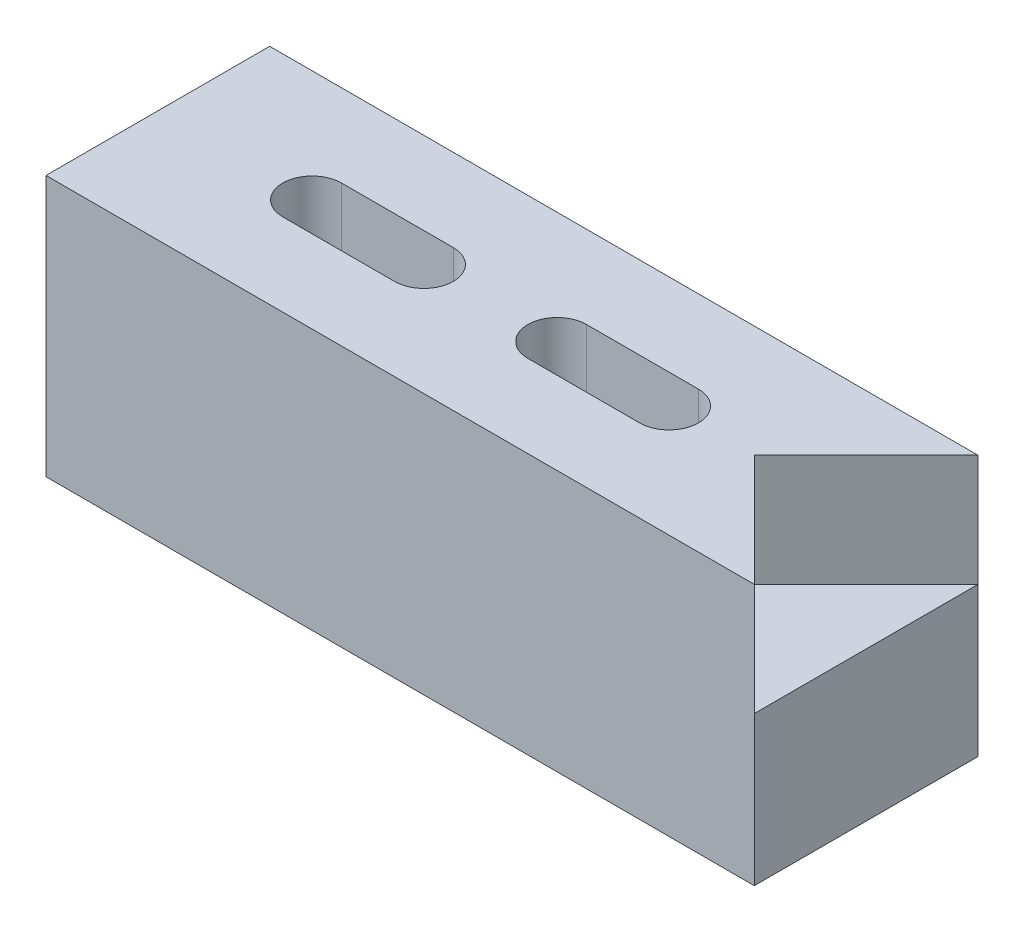
SolidWorks part; units mm, degrees
ref_plane "Front Plane" through (0, 0, 0) normal (0, 0, 1) x (1, 0, 0)
ref_plane "Top Plane" through (0, 0, 0) normal (0, 1, 0) x (1, 0, 0)
ref_plane "Right Plane" through (0, 0, 0) normal (1, 0, 0) x (0, 0, -1)
sketch "Sketch1" plane through (0, 0, 0) normal (0, 0, 1) x (1, 0, 0)
  line L0 (0, 0) -> (48.26, 0)
  line L6 (0, 0) -> (0, 17.78)
  line L10 (0, 17.78) -> (48.26, 17.78)
  line L11 (48.26, 0) -> (48.26, 17.78)
  dimension "D1" = 48.26
  dimension "D2" = 17.78
extrude "Boss-Extrude1" add sketch "Sketch1" against normal blind 15.24
sketch "Sketch3" plane through (0, 17.78, 0) normal (0, 1, 0) x (1, 0, 0)
  line L0 (48.26, 15.24) -> (40.64, 7.62)
  line L1 (40.64, 7.62) -> (48.26, 0)
  line L4 (48.26, 15.24) -> (48.26, 0)
  point P5 (36.83, 6.35)
  dimension "D2" = 90
extrude "Cut-Extrude1" cut sketch "Sketch3" against normal blind 7.62
sketch "Sketch4" plane through (0, 17.78, 0) normal (0, 1, 0) x (1, 0, 0)
  line L0 (34.83, 7.62) -> (27.21, 7.62) construction
  line L1 (34.83, 5.62) -> (27.21, 5.62)
  line L2 (34.83, 9.62) -> (27.21, 9.62)
  line L3 (18.13, 7.62) -> (10.51, 7.62) construction
  line L4 (18.13, 5.62) -> (10.51, 5.62)
  line L5 (18.13, 9.62) -> (10.51, 9.62)
  line L6 (48.26, 0) -> (0, 0) construction
  arc A0 (34.83, 5.62) -> (34.83, 9.62) centre (34.83, 7.62) ccw
  arc A1 (27.21, 9.62) -> (27.21, 5.62) centre (27.21, 7.62) ccw
  arc A2 (18.13, 5.62) -> (18.13, 9.62) centre (18.13, 7.62) ccw
  arc A3 (10.51, 9.62) -> (10.51, 5.62) centre (10.51, 7.62) ccw
  point P2 (31.02, 7.62)
  point P7 (14.32, 7.62)
  point P14 (36.83, 7.62)
  point P16 (8.51, 7.62)
  point P18 (20.13, 7.62)
  point P19 (25.21, 7.62)
  dimension "D1" = 4
  dimension "D2" = 3.81
  dimension "D3" = 7.62
  dimension "D4" = 7.62
  dimension "D5" = 5.08
extrude "Cut-Extrude2" cut sketch "Sketch4" against normal through all
